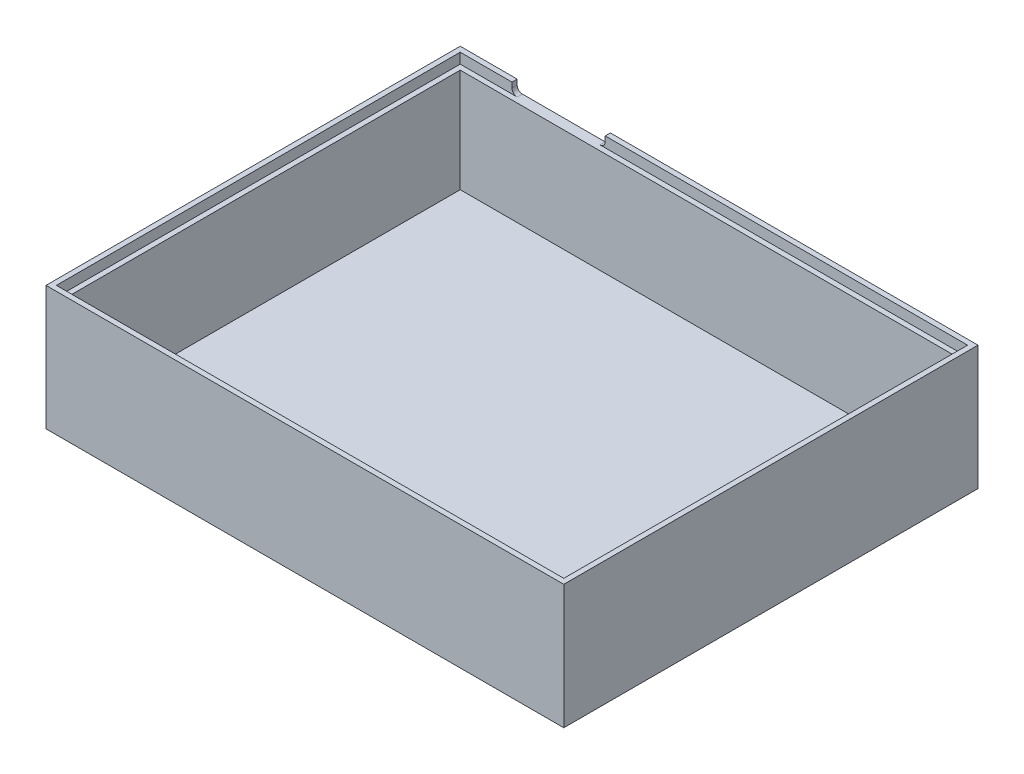
SolidWorks part; units mm, degrees
ref_plane "Plan de face" through (0, 0, 0) normal (0, 0, 1) x (1, 0, 0)
ref_plane "Plan de dessus" through (0, 0, 0) normal (0, 1, 0) x (1, 0, 0)
ref_plane "Plan de droite" through (0, 0, 0) normal (1, 0, 0) x (0, 0, -1)
sketch "Esquisse1" plane through (0, 0, 0) normal (0, 1, 0) x (1, 0, 0)
  line L1 (50, 40) -> (-50, 40)
  line L2 (50, 40) -> (50, -40)
  line L3 (50, -40) -> (-50, -40)
  line L4 (-50, 40) -> (-50, -40)
  line L5 (50, 40) -> (-50, -40) construction
  line L6 (50, -40) -> (-50, 40) construction
  point P0 (0, 0)
  dimension "D1" = 100
  dimension "D2" = 80
extrude "Boss.-Extru.1" add sketch "Esquisse1" along normal blind 2
sketch "Esquisse2" plane through (0, 2, 0) normal (0, 1, 0) x (1, 0, 0)
  line L0 (-48, 38) -> (-48, -38)
  line L1 (-48, -38) -> (48, -38)
  line L2 (48, -38) -> (48, 38)
  line L3 (48, 38) -> (-48, 38)
  line L4 (-50, 40) -> (-50, -40)
  line L5 (-50, -40) -> (50, -40)
  line L6 (50, -40) -> (50, 40)
  line L7 (50, 40) -> (-50, 40)
  line L8 (-50, 40) -> (-50, -40)
  line L9 (-50, -40) -> (50, -40)
  line L10 (50, -40) -> (50, 40)
  line L11 (50, 40) -> (-50, 40)
  line M10 (-50, 40) -> (-50, -40)
  line M11 (-50, -40) -> (50, -40)
  line M12 (50, -40) -> (50, 40)
  line M13 (50, 40) -> (-50, 40)
  dimension "D1" = 0
  dimension "D2" = 2
extrude "Boss.-Extru.2" add sketch "Esquisse2" along normal blind 20 contours L3 L2 L1 L0 M13 M10 M11 M12 region at (0, 2, -38.7194)
sketch "Esquisse5" plane through (0, 22, 0) normal (0, 1, 0) x (1, 0, 0)
  line L8 (49, -39) -> (49, 39)
  line L9 (-49, -39) -> (49, -39)
  line L10 (-49, 39) -> (-49, -39)
  line L11 (49, 39) -> (-49, 39)
  line L12 (49, -39) -> (49, 39)
  line L13 (-49, -39) -> (49, -39)
  line L14 (-49, 39) -> (-49, -39)
  line L15 (49, 39) -> (-49, 39)
  line L16 (50, -40) -> (50, 40) construction
  line L17 (-50, -40) -> (50, -40) construction
  line L18 (-50, 40) -> (-50, -40) construction
  line L19 (50, 40) -> (-50, 40) construction
  line L20 (50, -40) -> (50, 40)
  line L21 (-50, -40) -> (50, -40)
  line L22 (-50, 40) -> (-50, -40)
  line L23 (50, 40) -> (-50, 40)
  dimension "D1" = 1
extrude "Boss.-Extru.3" add sketch "Esquisse5" along normal blind 2
sketch "Esquisse6" plane through (0, 0, -40) normal (0, 0, -1) x (-1, 0, 0)
  line L0 (21, 24) -> (21, 22)
  line L1 (50, 24) -> (-50, 24) construction
  line L3 (21, 22) -> (39, 22)
  line L4 (39, 22) -> (39, 24)
  line L5 (39, 24) -> (21, 24)
  line L6 (50, 24) -> (50, 0) construction
  point P4 (0, 0)
  point P6 (0, 0)
  point P9 (0, 0)
  point P10 (21.8819, 24)
  point P11 (0, 0)
  dimension "D1" = 18
  dimension "D2" = 11
  dimension "D3" = 2
extrude "Enlèv. mat.-Extru.3" cut sketch "Esquisse6" against normal blind 10
fillet "Congé1" radius 1 2 edges at (-21, 22, -39.5) (-39, 22, -39.5)
